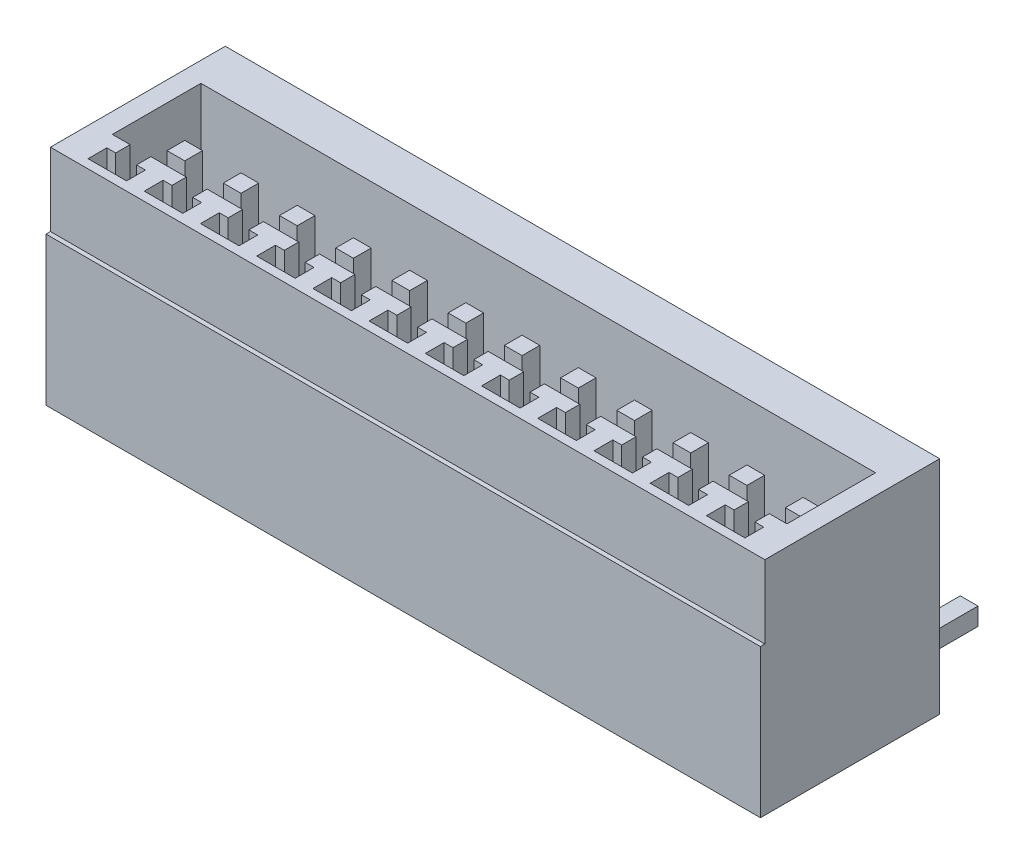
SolidWorks part; units mm, degrees
ref_plane "Front Plane" through (0, 0, 0) normal (0, 0, 1) x (1, 0, 0)
ref_plane "Top Plane" through (0, 0, 0) normal (0, 1, 0) x (1, 0, 0)
ref_plane "Right Plane" through (0, 0, 0) normal (1, 0, 0) x (0, 0, -1)
sketch "Sketch1" plane through (0, 0, 0) normal (0, 0, 1) x (1, 0, 0)
  line L0 (12.7, 0) -> (15.24, 0) construction
  line L1 (12.7, 8.8) -> (15.24, 8.8)
  line L2 (12.7, 8.8) -> (12.7, -1.2)
  line L3 (12.7, -1.2) -> (15.24, -1.2)
  line L4 (15.24, 8.8) -> (15.24, -1.2)
  line L5 (13.97, 8.8) -> (13.97, -1.2) construction
  line L7 (13.57, -0.4) -> (14.37, -0.4)
  line L8 (13.57, -0.4) -> (13.57, 0.4)
  line L9 (13.57, 0.4) -> (14.37, 0.4)
  line L10 (14.37, -0.4) -> (14.37, 0.4)
  line L11 (13.57, -0.4) -> (14.37, 0.4) construction
  line L12 (13.57, 0.4) -> (14.37, -0.4) construction
  point P15 (13.97, 0)
  dimension "D1" = 0.8
  dimension "D2" = 1.2
  dimension "D3" = 10
  dimension "D4" = 2.54
  dimension "D5" = 13.97
extrude "Boss-Extrude1" add sketch "Sketch1" along normal blind 8.1 contours L4 L3 L2 L1
extrude "Boss-Extrude2" add sketch "Sketch1<3>" against normal blind 3.5 contours L10 L9 L8 L7
sketch "Sketch1<3>" plane through (0, 0, 0) normal (0, 0, 1) x (1, 0, 0) same geometry as "Sketch1"
sketch "Sketch2" plane through (0, 0, 8.1) normal (0, 0, 1) x (1, 0, 0)
  line L0 (15.24, 8.8) -> (15.24, -1.2) construction
  line L1 (12.7, 8.8) -> (15.24, 8.8)
  line L2 (12.7, 8.8) -> (12.7, 5.5)
  line L3 (12.7, 5.5) -> (15.24, 5.5)
  line L4 (15.24, 8.8) -> (15.24, 5.5)
  line L5 (12.7, -1.2) -> (15.24, -1.2) construction
  dimension "D1" = 6.7
extrude "Cut-Extrude1" cut sketch "Sketch2" against normal blind 0.2
sketch "Sketch3" plane through (0, 8.8, 0) normal (0, 1, 0) x (1, 0, 0)
  line L0 (15.24, -7.9) -> (15.24, 0) construction
  line L1 (15.24, -2) -> (12.7, -2)
  line L2 (15.24, -2) -> (15.24, -6)
  line L3 (15.24, -6) -> (14.44, -6)
  line L4 (12.7, -2) -> (12.7, -6)
  line L6 (12.7, -7.9) -> (12.7, 0) construction
  line L8 (14.44, -6) -> (14.44, -6.65)
  line L10 (13.5, -6) -> (13.5, -6.65)
  line L11 (14.84, -6.65) -> (14.44, -6.65)
  line L12 (14.84, -6.65) -> (14.84, -7.5)
  line L13 (14.84, -7.5) -> (13.1, -7.5)
  line L14 (13.1, -6.65) -> (13.1, -7.5)
  line L17 (13.5, -6.65) -> (13.1, -6.65)
  line L18 (13.5, -6) -> (12.7, -6)
  line L19 (12.7, 0) -> (15.24, 0) construction
  point P6 (14.7728, -7.5)
  point P19 (0, -7.9)
  dimension "D1" = 2
  dimension "D2" = 6
  dimension "D3" = 0.65
  dimension "D4" = 7.5
  dimension "D5" = 0.8
  dimension "D6" = 0.4
extrude "Cut-Extrude2" cut sketch "Sketch3" against normal blind 6
sketch "Sketch4" plane through (0, 2.8, 0) normal (0, 1, 0) x (1, 0, 0)
  line L0 (0, 0) -> (0, -4) construction
  line L1 (12.7, 0) -> (15.24, 0) construction
  line L2 (13.57, -3.6) -> (14.37, -3.6)
  line L3 (13.57, -3.6) -> (13.57, -4.4)
  line L4 (13.57, -4.4) -> (14.37, -4.4)
  line L5 (14.37, -3.6) -> (14.37, -4.4)
  line L6 (13.57, -3.6) -> (14.37, -4.4) construction
  line L7 (13.57, -4.4) -> (14.37, -3.6) construction
  line L8 (13.97, -2) -> (13.97, -4) construction
  line L9 (15.24, -2) -> (12.7, -2) construction
  point P13 (13.97, -4)
  dimension "D1" = 0.8
  dimension "D2" = 4
extrude "Boss-Extrude3" add sketch "Sketch4" along normal blind 5
pattern_linear "LPattern1" count 12 spacing 2.54 along (1, 0, 0) of "Boss-Extrude2", "Cut-Extrude1", "Cut-Extrude2", "Boss-Extrude3"
sketch "Sketch5" plane through (15.24, 0, 0) normal (1, 0, 0) x (0, 0, -1)
  line L1 (-8.1, -1.2) -> (0, -1.2)
  line L2 (-8.1, -1.2) -> (-8.1, 5.5)
  line L3 (-7.9, 8.8) -> (0, 8.8)
  line L4 (0, -1.2) -> (0, 8.8)
  line L7 (-8.1, 5.5) -> (-7.9, 5.5)
  line L8 (-7.9, 8.8) -> (-7.9, 5.5)
extrude "Boss-Extrude4" add sketch "Sketch5" along normal blind 0.9
extrude "Boss-Extrude5" add sketch "Sketch5<2>" against normal blind 0.9 from offset 30.48 offset against normal yes
sketch "Sketch5<2>" plane through (15.24, 0, 0) normal (1, 0, 0) x (0, 0, -1) same geometry as "Sketch5"
combine bodies "Combine1" operation type add bodies to combine 106 107 108 109 114 115 116 117 118 119 120 110 111
